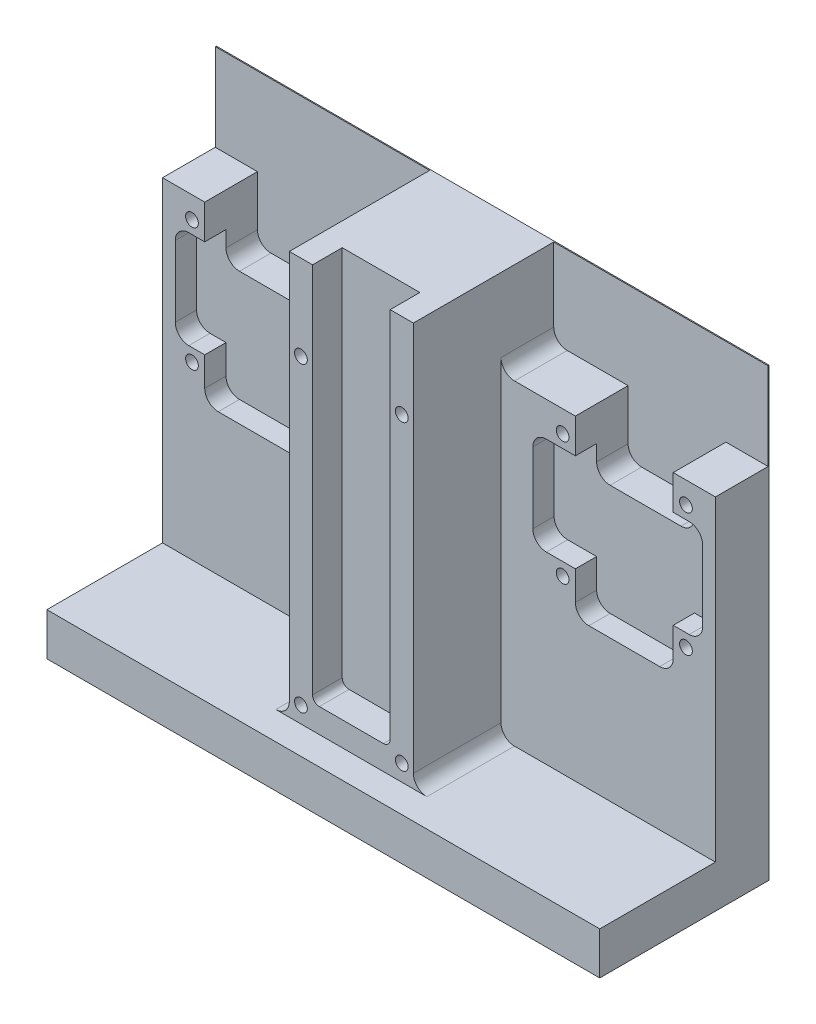
SolidWorks part; units mm, degrees
ref_plane "Front Plane" through (0, 0, 0) normal (0, 0, 1) x (1, 0, 0)
ref_plane "Top Plane" through (0, 0, 0) normal (0, 1, 0) x (1, 0, 0)
ref_plane "Right Plane" through (0, 0, 0) normal (1, 0, 0) x (0, 0, -1)
sketch "Sketch1" plane through (0, 0, 0) normal (0, 0, 1) x (1, 0, 0)
  line L0 (0, 0) -> (130, 0)
  line L1 (0, 0) -> (0, -104.86)
  line L2 (0, -104.86) -> (130, -104.86)
  line L3 (130, -104.86) -> (130, 0)
  dimension "D1" = 130
  dimension "D2" = 104.86
extrude "Boss-Extrude1" add sketch "Sketch1" along normal blind 39.84
sketch "Sketch2" plane through (0, 0, 39.84) normal (0, 0, 1) x (1, 0, 0)
  line L0 (130, 0) -> (130, -94.86)
  line L1 (130, -104.86) -> (130, 0) construction
  line L2 (130, -94.86) -> (0, -94.86)
  line L3 (0, 0) -> (0, -104.86) construction
  line L4 (0, -94.86) -> (0, 0)
  line L5 (0, 0) -> (130, 0)
  dimension "D1" = 94.86
extrude "Cut-Extrude1" cut sketch "Sketch2" against normal blind 6.6
sketch "Sketch3" plane through (0, 0, 33.24) normal (0, 0, 1) x (1, 0, 0)
  line L0 (55.875, 0) -> (55.875, -89.15)
  line L1 (130, 0) -> (0, 0) construction
  line L2 (55.875, -89.15) -> (74.125, -89.15)
  line L3 (74.125, -89.15) -> (74.125, 0)
  line L4 (74.125, 0) -> (55.875, 0)
  line L5 (130, -94.86) -> (130, 0) construction
  dimension "D1" = 18.25
  dimension "D2" = 55.875
  dimension "D3" = 89.15
extrude "Cut-Extrude2" cut sketch "Sketch3" against normal blind 6.98
sketch "Sketch5" plane through (0, 0, 33.24) normal (0, 0, 1) x (1, 0, 0)
  line L0 (79.585, 0) -> (79.585, -94.86)
  line L1 (130, 0) -> (74.125, 0) construction
  line L2 (0, -94.86) -> (130, -94.86) construction
  line L3 (79.585, -94.86) -> (130, -94.86)
  line L4 (130, -94.86) -> (130, 0)
  line L5 (130, 0) -> (79.585, 0)
  line L6 (50.415, 0) -> (50.415, -94.86)
  line L7 (55.875, 0) -> (0, 0) construction
  line L8 (50.415, -94.86) -> (0, -94.86)
  line L9 (0, -94.86) -> (0, 0)
  line L10 (0, 0) -> (50.415, 0)
  line L11 (55.875, 0) -> (55.875, -89.15) construction
  line L12 (74.125, -89.15) -> (74.125, 0) construction
  dimension "D1" = 5.46
  dimension "D2" = 5.46
extrude "Cut-Extrude3" cut sketch "Sketch5" against normal blind 20.6
sketch "Sketch6" plane through (0, 0, 12.64) normal (0, 0, 1) x (1, 0, 0)
  line L0 (50.415, -94.86) -> (50.415, 0) construction
  line L1 (74.125, 0) -> (55.875, 0) construction
  line L2 (79.585, 0) -> (79.585, -94.86) construction
  circle A0 centre (35.925, -25.6) radius 1.5
  circle A1 centre (6.925, -25.6) radius 1.5
  circle A2 centre (35.925, -54.6) radius 1.5
  circle A3 centre (6.925, -54.6) radius 1.5
  circle A4 centre (94.075, -25.6) radius 1.5
  circle A5 centre (123.075, -25.6) radius 1.5
  circle A6 centre (94.075, -54.6) radius 1.5
  circle A7 centre (123.075, -54.6) radius 1.5
  dimension "D2" = 3
  dimension "D3" = 25.6
  dimension "D4" = 29
  dimension "D5" = 29
  dimension "D6" = 29
  dimension "D8" = 14.49
  dimension "D9" = 29
  dimension "D10" = 29
  dimension "D11" = 29
  dimension "D1" = 14.49
  dimension "D7" = 29
  dimension "D12" = 29
  dimension "D13" = 25.6
extrude "Cut-Extrude4" cut sketch "Sketch6" against normal blind 12.4
sketch "Sketch7" plane through (0, 0, 12.64) normal (0, 0, 1) x (1, 0, 0)
  line L0 (50.415, -94.86) -> (50.415, 0) construction
  line L1 (0, 0) -> (50.415, 0)
  line L2 (0, 0) -> (0, -20.5)
  line L3 (0, -20.5) -> (50.415, -20.5)
  line L4 (50.415, 0) -> (50.415, -20.5)
  line L5 (130, -94.86) -> (130, 0) construction
  line L6 (79.585, 0) -> (130, 0)
  line L7 (79.585, 0) -> (79.585, -20.5)
  line L8 (79.585, -20.5) -> (130, -20.5)
  line L9 (130, 0) -> (130, -20.5)
  dimension "D1" = 20.5
  dimension "D2" = 20.5
extrude "Cut-Extrude5" cut sketch "Sketch7" against normal blind 12.4
sketch "Sketch9" plane through (0, 0, 12.64) normal (0, 0, 1) x (1, 0, 0)
  line L0 (97.075, -20.5) -> (97.075, -35.5)
  line L1 (79.585, -20.5) -> (130, -20.5) construction
  line L2 (97.075, -35.5) -> (120.075, -35.5)
  line L3 (120.075, -35.5) -> (120.075, -20.5)
  line L4 (120.075, -20.5) -> (97.075, -20.5)
  line L5 (9.925, -20.5) -> (9.925, -35.5)
  line L6 (0, -20.5) -> (50.415, -20.5) construction
  line L7 (9.925, -35.5) -> (32.925, -35.5)
  line L8 (32.925, -35.5) -> (32.925, -20.5)
  line L9 (0, -20.5) -> (50.415, -20.5) construction
  line L10 (32.925, -20.5) -> (9.925, -20.5)
  circle A0 centre (123.075, -25.6) radius 1.5 construction
  circle A1 centre (94.075, -25.6) radius 1.5 construction
  circle A2 centre (6.925, -25.6) radius 1.5 construction
  circle A3 centre (35.925, -25.6) radius 1.5 construction
  dimension "D1" = 3
  dimension "D4" = 3
  dimension "D2" = 3
  dimension "D3" = 15
  dimension "D5" = 3
  dimension "D6" = 15
extrude "Cut-Extrude7" cut sketch "Sketch9" against normal up to surface (12.4 mm away) up to face at (104.7925, -10.25, 0.24)
sketch "Sketch10" plane through (0, 0, 12.64) normal (0, 0, 1) x (1, 0, 0)
  line L0 (9.925, -28.6) -> (3, -28.6)
  line L1 (9.925, -35.5) -> (9.925, -20.5) construction
  line L2 (3, -28.6) -> (3, -51.6)
  line L3 (3, -51.6) -> (9.925, -51.6)
  line L4 (9.925, -51.6) -> (9.925, -61.6)
  line L5 (9.925, -61.6) -> (32.925, -61.6)
  line L6 (32.925, -61.6) -> (32.925, -51.6)
  line L7 (32.925, -51.6) -> (42.925, -51.6)
  line L8 (42.925, -51.6) -> (42.925, -28.6)
  line L9 (42.925, -28.6) -> (32.925, -28.6)
  line L10 (32.925, -35.5) -> (32.925, -20.5) construction
  line L11 (32.925, -28.6) -> (32.925, -35.5)
  line L12 (32.925, -35.5) -> (9.925, -35.5)
  line L13 (32.925, -35.5) -> (9.925, -35.5) construction
  line L14 (9.925, -35.5) -> (9.925, -28.6)
  line L16 (0, -20.5) -> (0, -94.86) construction
  line L17 (97.075, -28.6) -> (87.075, -28.6)
  line L18 (97.075, -20.5) -> (97.075, -35.5) construction
  line L19 (87.075, -28.6) -> (87.075, -51.6)
  line L20 (87.075, -51.6) -> (97.075, -51.6)
  line L21 (97.075, -51.6) -> (97.075, -61.6)
  line L22 (97.075, -61.6) -> (120.075, -61.6)
  line L23 (120.075, -61.6) -> (120.075, -51.6)
  line L24 (120.075, -51.6) -> (127, -51.6)
  line L25 (127, -51.6) -> (127, -28.6)
  line L26 (127, -28.6) -> (120.075, -28.6)
  line L27 (120.075, -35.5) -> (120.075, -20.5) construction
  line L28 (120.075, -28.6) -> (120.075, -35.5)
  line L29 (120.075, -35.5) -> (97.075, -35.5)
  line L30 (97.075, -35.5) -> (97.075, -28.6)
  line L31 (130, -94.86) -> (130, -20.5) construction
  circle A0 centre (6.925, -25.6) radius 1.5 construction
  circle A1 centre (35.925, -25.6) radius 1.5 construction
  circle A2 centre (6.925, -54.6) radius 1.5 construction
  circle A3 centre (6.925, -54.6) radius 1.5 construction
  circle A4 centre (35.925, -54.6) radius 1.5 construction
  circle A5 centre (94.075, -25.6) radius 1.5 construction
  circle A6 centre (94.075, -54.6) radius 1.5 construction
  circle A7 centre (123.075, -54.6) radius 1.5 construction
  circle A8 centre (123.075, -25.6) radius 1.5 construction
  dimension "D3" = 3
  dimension "D6" = 3
  dimension "D10" = 3
  dimension "D14" = 3
  dimension "D1" = 3
  dimension "D2" = 3
  dimension "D4" = 3
  dimension "D5" = 3
  dimension "D7" = 10
  dimension "D8" = 3
  dimension "D9" = 10
  dimension "D11" = 3
  dimension "D12" = 3
  dimension "D13" = 3
  dimension "D15" = 3
  dimension "D16" = 10
  dimension "D17" = 3
  dimension "D18" = 10
extrude "Cut-Extrude8" cut sketch "Sketch10" against normal blind 5
sketch "Sketch11" plane through (0, 0, 33.24) normal (0, 0, 1) x (1, 0, 0)
  line L0 (55.875, 0) -> (50.415, 0) construction
  line L1 (55.875, 0) -> (55.875, -89.15) construction
  line L2 (74.125, -89.15) -> (74.125, 0) construction
  line L3 (79.585, 0) -> (74.125, 0) construction
  circle A0 centre (53.145, -20) radius 1.5
  circle A1 centre (76.855, -20) radius 1.5
  circle A2 centre (53.145, -91) radius 1.5
  circle A3 centre (76.855, -91) radius 1.5
  point P4 (53.145, 0)
  dimension "D1" = 20
  dimension "D2" = 2.73
  dimension "D3" = 2.73
  dimension "D5" = 91
  dimension "D4" = 20
extrude "Cut-Extrude9" cut sketch "Sketch11" against normal blind 15
fillet "Fillet2" radius 3.175 1 edges at (3, -51.6, 10.14)
fillet "Fillet3" radius 3.175 15 edges at (120.075, -61.6, 10.14) (97.075, -61.6, 10.14) (127, -28.6, 10.14) (127, -51.6, 10.14) (87.075, -28.6, 10.14) (87.075, -51.6, 10.14) (79.585, -20.5, 6.44) (50.415, -20.5, 6.44) (32.925, -35.5, 3.94) (9.925, -35.5, 3.94) (3, -28.6, 10.14) (42.925, -28.6, 10.14) (42.925, -51.6, 10.14) (32.925, -61.6, 10.14) (9.925, -61.6, 10.14)
fillet "Fillet4" radius 3.175 2 edges at (120.075, -35.5, 3.94) (97.075, -35.5, 3.94)
fillet "Fillet5" radius 1.5875 2 edges at (74.125, -89.15, 29.75) (55.875, -89.15, 29.75)
fillet "Fillet6" radius 3.175 2 edges at (79.585, -94.86, 22.94) (50.415, -94.86, 22.94)
